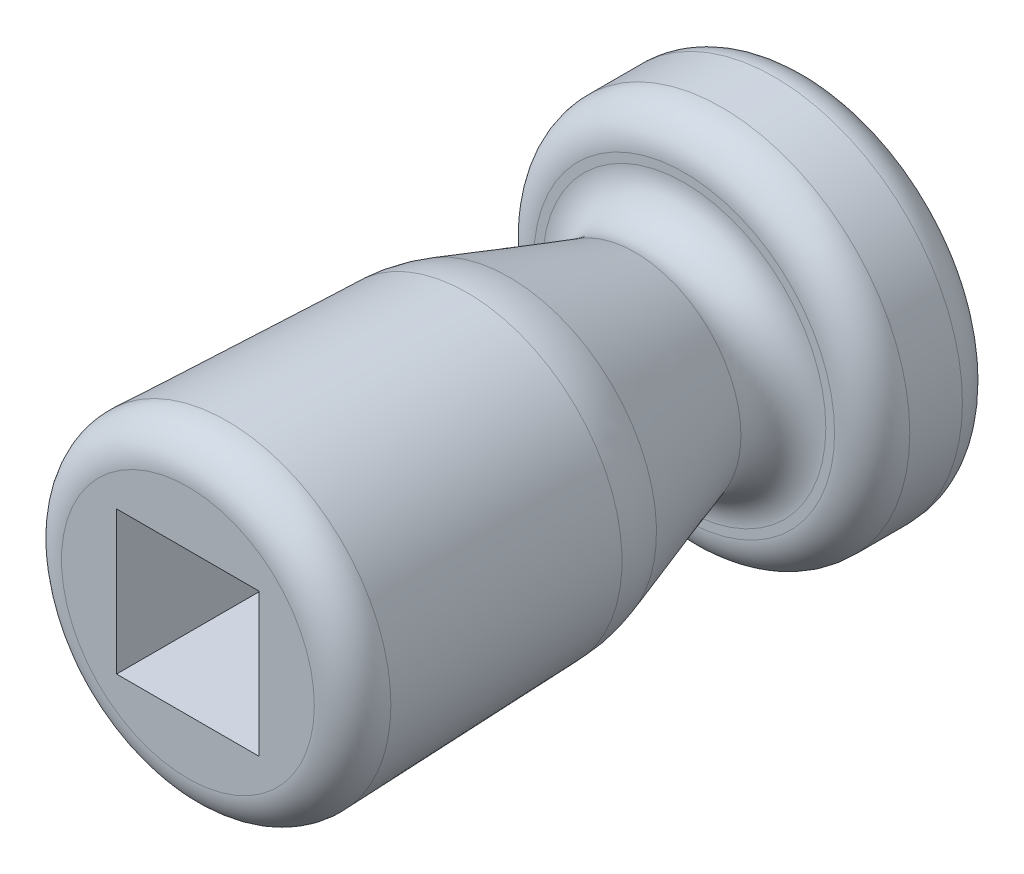
SolidWorks part; units mm, degrees
ref_plane "前视基准面" through (0, 0, 0) normal (0, 0, 1) x (1, 0, 0)
ref_plane "上视基准面" through (0, 0, 0) normal (0, 1, 0) x (1, 0, 0)
ref_plane "右视基准面" through (0, 0, 0) normal (1, 0, 0) x (0, 0, -1)
sketch "草图1" plane through (0, 0, 0) normal (0, 0, 1) x (1, 0, 0)
  circle A0 centre (0, 0) radius 2.5
extrude "凸台-拉伸1" add sketch "草图1" along normal blind 1.7
ref_plane "基准面1" through (0, 0, 4.3) normal (0, 0, 1) x (1, 0, 0)
sketch "草图2" plane through (0, 0, 1.7) normal (0, 0, 1) x (1, 0, 0)
  circle A0 centre (0, 0) radius 1.2
fillet "圆角7" radius 0.5 1 edges at (2.5, 0, 0) type face fillet first side face at (2.5, 0, 0) second side face at (2.5, 0, 1.7)
sketch "草图6" plane through (0, 0, 4.3) normal (0, 0, 1) x (1, 0, 0)
  circle A0 centre (0, 0) radius 2.0506
  point P0 (0, 0)
loft "放样1" add profiles "草图2", "草图6" connector at (0.6657, 0.9984, 1.7) connector at (1.45, 1.45, 4.3)
ref_plane "基准面2" through (0, 0, 8.3) normal (0, 0, 1) x (1, 0, 0)
sketch "草图7" plane through (0, 0, 4.3) normal (0, 0, 1) x (1, 0, 0)
  circle A0 centre (0, 0) radius 2.0506
sketch "草图8" plane through (0, 0, 8.3) normal (0, 0, 1) x (1, 0, 0)
  circle A0 centre (0, 0) radius 2.2
loft "放样3" add profiles "草图7", "草图8" connector at (1.45, 1.45, 4.3) connector at (1.7238, 1.3669, 8.3)
sketch "草图10" plane through (0, 0, 8.3) normal (0, 0, 1) x (1, 0, 0)
  line L1 (-0.9483, 0.9512) -> (0.9483, 0.9512)
  line L2 (-0.9483, 0.9512) -> (-0.9483, -0.9512)
  line L3 (-0.9483, -0.9512) -> (0.9483, -0.9512)
  line L4 (0.9483, 0.9512) -> (0.9483, -0.9512)
  line L5 (-0.9483, 0.9512) -> (0.9483, -0.9512) construction
  line L6 (-0.9483, -0.9512) -> (0.9483, 0.9512) construction
  point P0 (0, 0)
extrude "切除-拉伸1" cut sketch "草图10" against normal blind 4
fillet "圆角13" radius 0.5 1 edges at (2.5, 0, 1.7) type face fillet first side face at (2.5, 0, 0.5) second side face at (2.5, 0, 1.7)
fillet "圆角17" radius 2 1 edges at (2.0506, 0, 4.3) type face fillet first side face at (1.2, 0, 1.7) second side face at (2.0506, 0, 4.3)
fillet "圆角18" radius 0.5 1 edges at (1.2, 0, 1.7) type face fillet first side face at (2, 0, 1.7) second side face at (1.9592, 0, 4.0276)
fillet "圆角19" radius 0.5 1 edges at (2.2, 0, 8.3) type face fillet first side face at (-2.0614, 0, 4.5882) second side face at (0, 0, 8.3)
